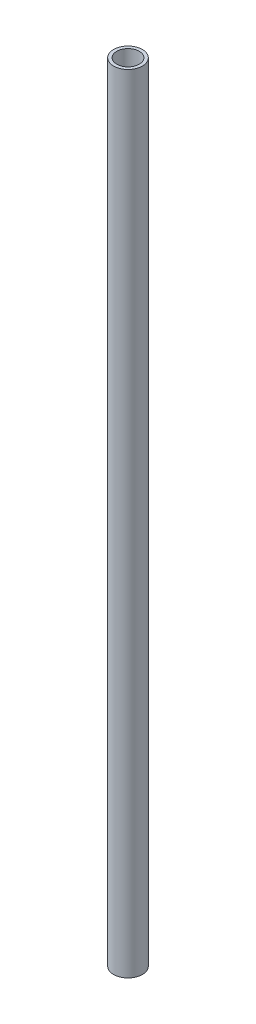
SolidWorks part; units mm, degrees
material "PVC Rigid"
ref_plane "Front Plane" through (0, 0, 0) normal (0, 0, 1) x (1, 0, 0)
ref_plane "Top Plane" through (0, 0, 0) normal (0, 1, 0) x (1, 0, 0)
ref_plane "Right Plane" through (0, 0, 0) normal (1, 0, 0) x (0, 0, -1)
sketch "Sketch1" plane through (0, 0, 0) normal (0, 1, 0) x (1, 0, 0)
  circle A0 centre (0, 0) radius 13.0683
  circle A1 centre (0, 0) radius 16.7005
  dimension "D1" = 33.401
  dimension "D2" = 26.1366
extrude "Boss-Extrude1" add sketch "Sketch1" along normal blind 914.4
